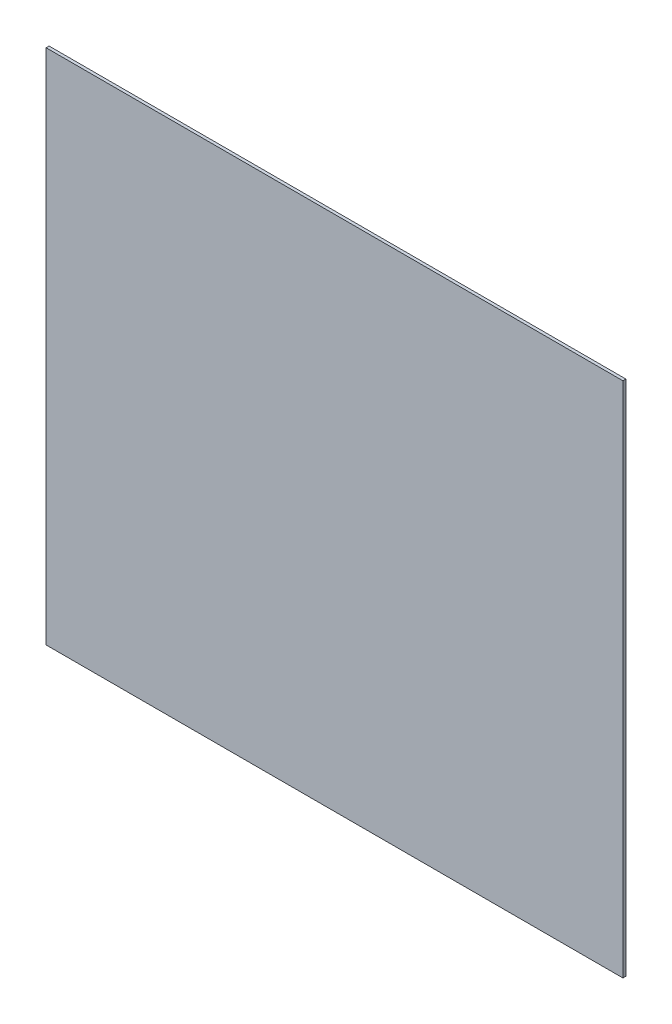
SolidWorks part; units mm, degrees
ref_plane "Ön Düzlem" through (0, 0, 0) normal (0, 0, 1) x (1, 0, 0)
ref_plane "Üst Düzlem" through (0, 0, 0) normal (0, 1, 0) x (1, 0, 0)
ref_plane "Sağ Düzlem" through (0, 0, 0) normal (1, 0, 0) x (0, 0, -1)
sketch "Çizim1" plane through (0, 0, 0) normal (0, 0, 1) x (1, 0, 0)
  line L1 (0, 0) -> (580, 0)
  line L2 (0, 0) -> (0, -520)
  line L3 (0, -520) -> (580, -520)
  line L4 (580, 0) -> (580, -520)
  dimension "D1" = 580
  dimension "D2" = 520
base flange "Taban-Flanş1" sketch "Çizim1" thickness 3 reverse thickness direction no parameters "D1"=2.5
sketch "Büküm-Çizgileri1" [suppressed] plane through (0, 0, 0) normal (0, 1, 0) x (1, 0, 0)
sketch "Sınırlandırma-Kutusu1" [suppressed] plane through (0, 0, 0) normal (0, 1, 0) x (1, 0, 0)
sheet metal parameters "Sac-Levha1" thickness 3 parameters "D1"=2.5
flat pattern "Düz-Çoğaltma1" [suppressed]
sketch "Büküm-Çizgileri2" plane through (0, 0, 0) normal (0, 1, 0) x (1, 0, 0)
sketch3d "Sınırlandırma-Kutusu2" [suppressed]
  line L0 (0, -520, 0) -> (580, -520, 0) construction
  line L1 (0, 0, 0) -> (580, 0, 0) construction
  line L2 (0, -520, 0) -> (0, 0, 0) construction
  line L3 (580, -520, 0) -> (580, 0, 0) construction
